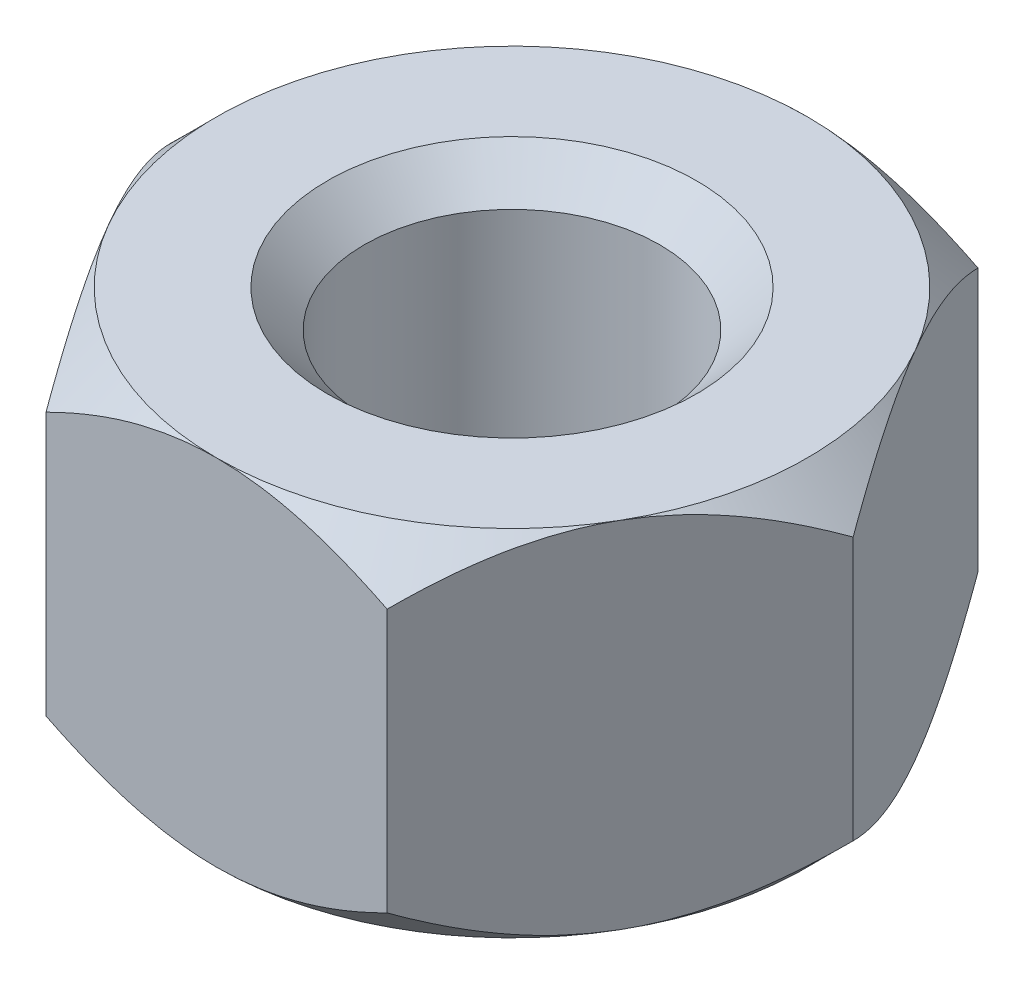
SolidWorks part; units mm, degrees
ref_plane "Front Plane" through (0, 0, 0) normal (0, 0, 1) x (1, 0, 0)
ref_plane "Top Plane" through (0, 0, 0) normal (0, 1, 0) x (1, 0, 0)
ref_plane "Right Plane" through (0, 0, 0) normal (1, 0, 0) x (0, 0, -1)
sketch "Sketch1" plane through (0, 0, 0) normal (0, 1, 0) x (1, 0, 0)
  line L1 (2.3094, 0) -> (1.1547, 2)
  line L2 (1.1547, 2) -> (-1.1547, 2)
  line L3 (-1.1547, 2) -> (-2.3094, 0)
  line L4 (-2.3094, 0) -> (-1.1547, -2)
  line L5 (-1.1547, -2) -> (1.1547, -2)
  line L6 (1.1547, -2) -> (2.3094, 0)
  circle A0 centre (0, 0) radius 2 construction
  circle A1 centre (0, 0) radius 1
  dimension "D2" = 2
  dimension "D1" = 4
extrude "Boss-Extrude1" add sketch "Sketch1" along normal blind 2.4 contours L5 L6 L1 L2 L3 L4 A1 region at (1.6791, 0, 0.9694)
sketch "Sketch2" plane through (0, 0, 0) normal (1, 0, 0) x (0, 0, -1)
  line L0 (2, 2.4) -> (3.05, 3.45)
  line L1 (3.05, 3.45) -> (3.05, 1.35)
  line L2 (3.05, 1.35) -> (2, 2.4)
  line L3 (2, 1.2) -> (7.8632, 1.2) construction
  line L4 (2, 2.4) -> (2, 0) construction
  line L5 (3.05, 1.05) -> (2, 0)
  line L6 (3.05, -1.05) -> (3.05, 1.05)
  line L7 (2, 0) -> (3.05, -1.05)
  dimension "D1" = 2.1
ref_axis "Axis1" through (0, 2.4, 0) along (0, -1, 0)
revolve "Cut-Revolve1" cut sketch "Sketch2" angle 360 about axis through (0, 2.4, 0) along (0, -1, 0)
sketch "Sketch4" plane through (0, 2.4, 0) normal (0, 1, 0) x (1, 0, 0)
  circle A0 centre (0, 0) radius 4
curve "Helix/Spiral1" [suppressed] pitch 1.25 height 5 turns 4
ref_plane "Plane1" [suppressed] through (0, 5, 4) normal (-0.9988, -0.0497, 0) x (0, 0, 1)
chamfer "Chamfer1" [suppressed] distance 0.5 angle 45
sketch "Sketch5" [suppressed] plane through (0, 5, 4) normal (-0.9988, -0.0497, 0) x (0, 0, 1)
  line L0 (0.4983, 0.146) -> (-0.8007, 0.896)
  line L1 (-0.8007, 0.896) -> (-0.8007, -0.604)
  line L2 (-0.8007, -0.604) -> (0.4983, 0.146)
  line L3 (-0.0006, -0.854) -> (0.1004, -0.854) construction
  dimension "D1" = 1.5
ref_axis "Axis2" through (0, 2.4, 0) along (0, -1, 0)
chamfer "Chamfer2" distance 0.25 angle 45 2 edges at (0, 2.4, 1) (0, 0, 1)
